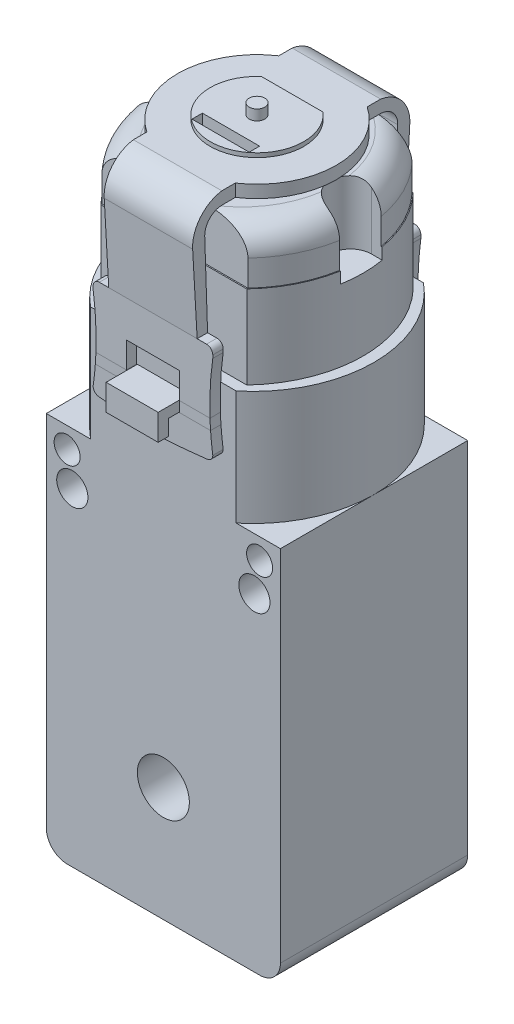
SolidWorks part; units mm, degrees
ref_plane "Alzado" through (0, 0, 0) normal (0, 0, 1) x (1, 0, 0)
ref_plane "Planta" through (0, 0, 0) normal (0, 1, 0) x (1, 0, 0)
ref_plane "Vista lateral" through (0, 0, 0) normal (1, 0, 0) x (0, 0, -1)
sketch "Croquis1" plane through (0, 0, 0) normal (0, 0, 1) x (1, 0, 0)
  line L0 (0, 17.25) -> (0, -19.25)
  line L1 (-11.25, 17.25) -> (11.25, 17.25)
  line L2 (11.25, 17.25) -> (11.25, -17.25)
  line L3 (9.25, -19.25) -> (-9.25, -19.25)
  line L4 (-11.25, 17.25) -> (-11.25, -17.25)
  arc A0 (11.25, -17.25) -> (9.25, -19.25) centre (9.25, -17.25) cw
  circle A1 centre (9.25, 15.25) radius 1.25
  circle A2 centre (8.75, 12.25) radius 1.5
  arc A3 (-11.25, -17.25) -> (-9.25, -19.25) centre (-9.25, -17.25) ccw
  circle A4 centre (-8.75, 12.25) radius 1.5
  circle A5 centre (-9.25, 15.25) radius 1.25
  point P9 (11.25, -19.25)
  dimension "D3" = 2
  dimension "D4" = 2.5
  dimension "D5" = 3
  dimension "D1" = 11.25
  dimension "D2" = 36.5
  dimension "D6" = 2
  dimension "D7" = 2.5
  dimension "D8" = 2
  dimension "D9" = 5
extrude "Saliente-Extruir1" add sketch "Croquis1" along normal blind 9 and the other way blind 9 contours L4 A3 L3 L0 L1 A4 A5 | A0 L2 L1 L0 L3 A2 A1 region at (5.5136, -1.3976, 0) region at (-5.5136, -1.3976, 0)
sketch "Croquis2" plane through (0, 17.25, 0) normal (0, 1, 0) x (1, 0, 0)
  line L0 (0, 9) -> (0, 0) construction
  line L1 (-11.25, 9) -> (11.25, 9) construction
  line L2 (-7, 9) -> (7, 9)
  line L3 (0, 0) -> (7, 0) construction
  line L4 (-7, -9) -> (7, -9)
  arc A0 (7, 9) -> (7, -9) centre (-0.4044, 0) cw
  arc A1 (-7, 9) -> (-7, -9) centre (0.4044, 0) ccw
  point P11 (0, -9)
  dimension "D1" = 7
extrude "Saliente-Extruir2" add sketch "Croquis2" along normal blind 11
sketch "Croquis3" plane through (0, 0, 0) normal (0, 0, 1) x (1, 0, 0)
  line L0 (0, -19.25) -> (0, -24.25) construction
  line L1 (9.25, -19.25) -> (-9.25, -19.25) construction
  line L2 (-2.5, -19.25) -> (2.5, -19.25)
  line L3 (2.5, -19.25) -> (2.5, -24.25)
  line L4 (2.5, -24.25) -> (-2.5, -24.25)
  line L5 (-2.5, -19.25) -> (-2.5, -24.25)
  circle A0 centre (0, -21.75) radius 1.25
  dimension "D3" = 2.5
  dimension "D1" = 2.5
  dimension "D2" = 5
extrude "Saliente-Extruir3" add sketch "Croquis3" along normal blind 1.5 and the other way blind 1.5
fillet "Redondeo1" radius 0.3 2 edges at (-2.5, -19.25, 0) (2.5, -19.25, 0)
sketch "Croquis4" plane through (0, 0, 0) normal (0, 0, 1) x (1, 0, 0)
  line L0 (9.25, -19.25) -> (-9.25, -19.25) construction
  line L1 (-3.337, -10.75) -> (3.722, -10.75) construction
  line L3 (0, 0) -> (0, -9.56) construction
  line L4 (-3.337, -5.75) -> (4.3804, -5.75) construction
  line L5 (11.25, 17.25) -> (7, 17.25) construction
  circle A0 centre (0, -8.25) radius 2.5
  dimension "D1" = 5
  dimension "D2" = 23
  dimension "D3" = 8.5
extrude "Cortar-Extruir1" cut sketch "Croquis4" against normal blind 10 and the other way blind 10
sketch "Croquis5" plane through (0, 0, -9) normal (0, 0, -1) x (-1, 0, 0)
  line L0 (0, 0) -> (0, 13.3907) construction
  line L1 (11.25, 17.25) -> (11.25, -17.25) construction
  line L2 (11.25, 17.25) -> (7, 17.25) construction
  line L3 (-9.25, -19.25) -> (9.25, -19.25) construction
  circle A0 centre (9.75, -2.25) radius 0.75
  circle A1 centre (9.25, -17.25) radius 1
  circle A3 centre (-9.25, -17.25) radius 1
  circle A4 centre (-9.75, -2.25) radius 0.75
  dimension "D1" = 1.5
  dimension "D4" = 2
  dimension "D2" = 1.5
  dimension "D3" = 19.5
  dimension "D5" = 2
  dimension "D6" = 2
extrude "Cortar-Extruir2" cut sketch "Croquis5" against normal blind 1.5
sketch "Croquis6" plane through (0, 0, -9) normal (0, 0, -1) x (-1, 0, 0)
  line L0 (0, 0) -> (0, 13.134) construction
  line L1 (-2.8, -19.25) -> (2.8, -19.25) construction
  circle A0 centre (0, 2.75) radius 2
  dimension "D1" = 4
  dimension "D2" = 22
extrude "Saliente-Extruir4" add sketch "Croquis6" along normal blind 2
sketch "Croquis7" plane through (0, 0, -9) normal (0, 0, -1) x (-1, 0, 0)
  line L2 (-3.0823, -11.75) -> (2.3777, -11.75) construction
  line L3 (-9.25, -19.25) -> (9.25, -19.25) construction
  circle A0 centre (0, -8.25) radius 3.5
  circle A1 centre (0, -8.25) radius 2.5
  dimension "D2" = 7.5
extrude "Saliente-Extruir5" add sketch "Croquis7" along normal blind 0.2
sketch "Croquis8" plane through (0, 28.25, 0) normal (0, 1, 0) x (1, 0, 0)
  line L0 (-7.0162, -8) -> (7.0162, -8)
  line L1 (-7, -9) -> (7, -9) construction
  line L2 (0, 0) -> (4.714, 0) construction
  line L3 (0, 0) -> (0, 4.6921) construction
  line L4 (-7.0162, 8) -> (7.0162, 8)
  line L5 (7.0162, 9) -> (7.0162, 6.4394) construction
  line L6 (7, 9) -> (11.25, 9) construction
  arc A0 (7.0162, 8) -> (7.0162, -8) centre (-1.4527, 0) cw
  arc A3 (-7.0162, 8) -> (-7.0162, -8) centre (1.4527, 0) ccw
  point P4 (0, -8)
  dimension "D3" = 11.65
  dimension "D1" = 1
extrude "Cortar-Extruir5" cut sketch "Croquis8" against normal blind 10
sketch "Croquis9" plane through (0, 0, 0) normal (0, 0, 1) x (1, 0, 0)
  line L0 (0, 28.25) -> (0, 16.5993) construction
  line L1 (-7, 28.25) -> (7, 28.25) construction
  line L2 (-2.9593, 24.7222) -> (3.0407, 24.7222)
  line L3 (3.0407, 24.7222) -> (3.0407, 21.7222)
  line L4 (3.0407, 21.7222) -> (-2.9593, 21.7222)
  line L5 (-2.9593, 21.7222) -> (-2.9593, 24.7222)
  dimension "D1" = 6
  dimension "D2" = 3
extrude "Cortar-Extruir6" cut sketch "Croquis9" against normal blind 10 and the other way blind 10
sketch "Croquis11" plane through (0, 0, 0) normal (1, 0, 0) x (0, 0, -1)
  line L0 (-9, 24.7222) -> (-11, 24.7222)
  line L1 (-11, 24.7222) -> (-11, 23.2222)
  line L2 (-11, 23.2222) -> (-12, 23.2222)
  line L3 (-12, 23.2222) -> (-12, 25.7222)
  line L4 (-12, 25.7222) -> (-9, 25.7222)
  line L5 (-9, 28.25) -> (-9, 17.25) construction
  line L6 (-9, 25.7222) -> (-9, 24.7222)
  dimension "D1" = 2
  dimension "D2" = 1.5
  dimension "D3" = 1
  dimension "D4" = 2.5
extrude "Saliente-Extruir6" add sketch "Croquis11" along normal blind 2.5 and the other way blind 2.5
mirror "Simetría1" about plane through (0, 0, 0) normal (0, 0, 1) of "Saliente-Extruir6"
sketch "Croquis12" plane through (0, 18.25, 0) normal (0, 1, 0) x (1, 0, 0)
  line L0 (-7.0162, 8) -> (7.0162, 8)
  line L1 (7.0162, -8) -> (-7.0162, -8)
  arc A0 (-7.0162, 8) -> (-7.0162, -8) centre (1.4527, 0) ccw
  arc A1 (7.0162, 8) -> (7.0162, -8) centre (-1.4527, 0) cw
extrude "Saliente-Extruir7" add sketch "Croquis12" along normal blind 18 separate body
sketch "Croquis13" plane through (0, 36.25, 0) normal (0, 1, 0) x (1, 0, 0)
  line L0 (-7.0162, 7.8859) -> (7.0162, 7.8859)
  line L1 (0, 0) -> (4.4298, 0) construction
  line L2 (-7.0162, -7.8859) -> (7.0162, -7.8859)
  line L3 (0, 0) -> (0, 5.9901) construction
  line L4 (-7.0162, 8) -> (-7.0162, 7.2605) construction
  line L5 (7.0162, 8) -> (7.0162, 7.0975) construction
  arc A0 (7.0162, 7.8859) -> (7.0162, -7.8859) centre (-1.4696, 0) cw
  arc A1 (-7.0162, 7.8859) -> (-7.0162, -7.8859) centre (1.4696, 0) ccw
extrude "Saliente-Extruir8" add sketch "Croquis13" along normal blind 5
fillet "Redondeo2" radius 2.5 2 edges at (-10.1147, 41.25, 0) (10.1147, 41.25, 0)
sketch "Croquis14" plane through (0, 41.25, 0) normal (0, 1, 0) x (1, 0, 0)
  line L0 (-2.964, 3.3859) -> (2.964, 3.3859)
  line L1 (3.0401, 7.8859) -> (-3.0401, 7.8859) construction
  line L2 (0, 0) -> (0, 6.8306) construction
  line L3 (0, 0) -> (0, -5.8728) construction
  line L4 (-2.75, -2.4984) -> (2.75, -2.4984)
  line L5 (2.75, -2.4984) -> (2.75, -3.4984)
  line L6 (-2.75, -2.4984) -> (-2.75, -3.4984)
  line L7 (-2.75, -3.4984) -> (2.75, -3.4984)
  arc A0 (-2.964, 3.3859) -> (2.964, 3.3859) centre (0, 0) ccw
  point P12 (0, -2.4984)
  dimension "D1" = 9
  dimension "D2" = 4.5
  dimension "D3" = 5.5
  dimension "D4" = 1
extrude "Saliente-Extruir9" add sketch "Croquis14" along normal blind 2 separate body contours L0 A0 L7 L6 L4 L5 region at (0, 41.25, 0.0162)
sketch "Croquis15" plane through (0, 43.25, 0) normal (0, 1, 0) x (1, 0, 0)
  circle A0 centre (0, 0) radius 0.75
  dimension "D1" = 1.5
extrude "Saliente-Extruir10" add sketch "Croquis15" along normal blind 1 separate body
sketch "Croquis16" plane through (0, 0, -9) normal (0, 0, -1) x (-1, 0, 0)
  line L0 (0, 0) -> (0, 20.8797) construction
  line L1 (2.349, 16.9) -> (8.25, 16.9) construction
  line L2 (11.25, 17.25) -> (7, 17.25) construction
  line L3 (11.25, 17.25) -> (11.25, -17.25) construction
  circle A0 centre (5.9941, 14.65) radius 2.25
  circle A1 centre (-5.9941, 14.65) radius 2.25
  dimension "D1" = 4.5
  dimension "D2" = 0.35
  dimension "D3" = 3
extrude "Cortar-Extruir7" cut sketch "Croquis16" against normal blind 2
sketch "Croquis17" plane through (0, 0, -7) normal (0, 0, -1) x (-1, 0, 0)
  line L0 (6.2973, 16.3735) -> (6.2973, 14.95)
  line L1 (6.2973, 14.95) -> (7.7182, 14.95)
  line L2 (5.9941, 14.65) -> (5.9941, 16.7103) construction
  line L3 (5.9941, 14.65) -> (8.0852, 14.65) construction
  line L4 (5.6908, 14.95) -> (4.27, 14.95)
  line L5 (5.6908, 16.3735) -> (5.6908, 14.95)
  line L6 (5.6908, 14.35) -> (4.27, 14.35)
  line L7 (5.6908, 12.9265) -> (5.6908, 14.35)
  line L8 (6.2973, 14.35) -> (7.7182, 14.35)
  line L9 (6.2973, 12.9265) -> (6.2973, 14.35)
  circle A0 centre (5.9941, 14.65) radius 1.75
  dimension "D1" = 3.5
  dimension "D2" = 0.3032
  dimension "D3" = 0.3
extrude "Saliente-Extruir11" add sketch "Croquis17" along normal blind 1.8 contours L5 A0 L4 | L1 A0 L0 | L9 A0 L8 | L0 A0 L5 L4 L6 L7 L9 L8 L1 | L6 A0 L7 region at (-6.8694, 15.523, -7) region at (-5.9941, 14.65, -7) region at (-5.1188, 15.523, -7) region at (-6.8694, 13.777, -7) region at (-5.1188, 13.777, -7)
sketch "Croquis18" plane through (0, 0, -8.8) normal (0, 0, -1) x (-1, 0, 0)
  line L0 (5.9941, 16.4) -> (5.9941, 14.65) construction
  line L1 (5.9941, 14.65) -> (7.7441, 14.65) construction
  line L2 (6.2941, 16.1877) -> (6.2941, 14.95)
  line L3 (6.2941, 14.95) -> (7.5318, 14.95)
  line L4 (5.6941, 14.95) -> (4.4563, 14.95)
  line L5 (5.6941, 16.1877) -> (5.6941, 14.95)
  line L6 (5.6941, 14.35) -> (4.4563, 14.35)
  line L7 (5.6941, 13.1123) -> (5.6941, 14.35)
  line L8 (6.2941, 13.1123) -> (6.2941, 14.35)
  line L9 (6.2941, 14.35) -> (7.5318, 14.35)
  circle A0 centre (5.9941, 14.65) radius 1.75 construction
  circle A1 centre (5.9941, 14.65) radius 1.75 construction
  arc A6 (4.4563, 14.95) -> (4.4563, 14.35) centre (5.9941, 14.65) ccw
  arc A7 (6.2941, 16.1877) -> (5.6941, 16.1877) centre (5.9941, 14.65) ccw
  arc A8 (7.5318, 14.35) -> (7.5318, 14.95) centre (5.9941, 14.65) ccw
  arc A9 (5.6941, 13.1123) -> (6.2941, 13.1123) centre (5.9941, 14.65) ccw
  dimension "D1" = 0.3
  dimension "D2" = 0.3
extrude "Cortar-Extruir8" cut sketch "Croquis18" against normal blind 0.5 contours L4 A6 L6 L7 A9 L8 L9 A8 L3 L2 A7 L5
mirror "Simetría4" about plane through (0, 0, 0) normal (1, 0, 0) of "Saliente-Extruir11"
mirror "Simetría5" about plane through (0, 0, 0) normal (1, 0, 0) of "Cortar-Extruir8"
ref_plane "Plano1" through (0, 41.65, 0) normal (0, 1, 0) x (1, 0, 0)
sketch "Croquis20" plane through (0, 41.65, 0) normal (0, 1, 0) x (1, 0, 0)
  line L0 (-2.964, 3.3859) -> (2.964, 3.3859)
  line L1 (-2.75, -3.4984) -> (-2.75, -2.4984)
  line L2 (-2.75, -2.4984) -> (2.75, -2.4984)
  line L3 (2.75, -2.4984) -> (2.75, -3.4984)
  line L4 (2.75, -3.4984) -> (-2.75, -3.4984)
  circle A0 centre (0, 0) radius 7.6307
  circle A1 centre (0, 0) radius 4.5
extrude "Saliente-Extruir13" add sketch "Croquis20" along normal blind 1.2 separate body contours A0 A1 | L0 A1 region at (0, 41.65, -3.8366) region at (-7.4148, 41.65, 0)
sketch "Croquis19" plane through (0, 0, 0) normal (1, 0, 0) x (0, 0, -1)
  line L0 (0, 0) -> (0, 53.3017) construction
  line L1 (9, 21.7222) -> (9, 24.7222)
  line L2 (9, 28.25) -> (9, 17.25) construction
  line L3 (12, 23.2222) -> (11, 23.2222) construction
  line L4 (9, 21.7222) -> (10, 21.7222)
  line L5 (10, 31.7222) -> (10, 25.8545)
  line L6 (9, 31.7222) -> (9.2741, 39.8972)
  line L7 (10, 21.7222) -> (10, 24.7222)
  line L9 (10, 21.7222) -> (10, 31.7222)
  line L10 (10, 31.7222) -> (10.4333, 39.3872)
  line L17 (9, 24.7222) -> (10, 24.7222)
  line L20 (9, 25.7222) -> (10, 25.7222)
  line L21 (10, 25.7222) -> (10, 25.8545)
  line L22 (9, 25.7222) -> (9, 31.7222)
  line L25 (-4.5012, 42.8648) -> (-4.5012, 41.7894)
  line L26 (8.3762, 41.65) -> (-8.3762, 41.65) construction
  line L29 (7.6307, 41.65) -> (7.6307, 42.85) construction
  line L30 (7.6307, 42.85) -> (7.6307, 41.65)
  line L31 (-10, 21.7222) -> (-10, 24.7222)
  line L32 (-9, 24.7222) -> (-10, 24.7222)
  line L33 (-9, 21.7222) -> (-9, 24.7222)
  line L34 (-9, 21.7222) -> (-10, 21.7222)
  line L35 (-10, 31.7222) -> (-10.4333, 39.3872)
  line L36 (-7.6307, 42.85) -> (-7.6307, 41.65)
  line L37 (-9, 31.7222) -> (-9.2741, 39.8972)
  line L38 (-9, 25.7222) -> (-9, 31.7222)
  line L39 (-9, 25.7222) -> (-10, 25.7222)
  line L40 (-10, 25.7222) -> (-10, 25.8545)
  line L41 (-10, 31.7222) -> (-10, 25.8545)
  arc A0 (9.2741, 39.8972) -> (7.6307, 41.65) centre (7.5783, 39.9541) ccw
  arc A1 (7.6307, 42.85) -> (10.4333, 39.3872) centre (7.1238, 39.5743) cw
  arc A2 (-7.6307, 42.85) -> (-10.4333, 39.3872) centre (-7.1238, 39.5743) ccw
  arc A3 (-9.2741, 39.8972) -> (-7.6307, 41.65) centre (-7.5783, 39.9541) cw
  dimension "D1" = 10
  dimension "D2" = 1.5
  dimension "D3" = 1
  dimension "D4" = 8.175
extrude "Saliente-Extruir12" add sketch "Croquis19" along normal blind 5.75 and the other way blind 5.75 separate body contours L6 L22 L20 L9 L5 L10 | L17 L1 L4 L7 | L25 L35 | L32 | L31 L32 L33 L34 region at (0, 34.7182, -9.4971) region at (0, 23.2222, -9.5) region at (0, 34.7182, 9.4971)
ref_plane "Plano2" through (0, 0, 10) normal (0, 0, 1) x (1, 0, 0)
sketch "Croquis23" plane through (0, 0, 10) normal (0, 0, 1) x (1, 0, 0)
  line L0 (0, 31.7222) -> (4.25, 31.7222)
  line L1 (-5.75, 31.7222) -> (5.75, 31.7222) construction
  line L2 (4.25, 31.7222) -> (4.25, 42.85)
  line L3 (-5.75, 42.85) -> (5.75, 42.85) construction
  line L4 (4.25, 42.85) -> (5.75, 42.85)
  line L5 (5.75, 42.85) -> (5.75, 31.7222)
  line L6 (5.75, 31.7222) -> (4.25, 31.7222)
  line L7 (0, 31.7222) -> (0, 41.8289) construction
  line L9 (-5.75, 31.7222) -> (-4.25, 31.7222)
  line L10 (-5.75, 42.85) -> (-5.75, 31.7222)
  line L11 (-4.25, 42.85) -> (-5.75, 42.85)
  line L12 (-4.25, 31.7222) -> (-4.25, 42.85)
  dimension "D1" = 4.25
extrude "Cortar-Extruir9" cut sketch "Croquis23" against normal blind 1.8 and the other way blind 1 contours L9 L12 L11 L10 | L6 L5 L4 L2 region at (5, 37.2861, 10) region at (-5, 37.2861, 10)
ref_plane "Plano3" through (0, 0, -10) normal (0, 0, 1) x (1, 0, 0)
sketch "Croquis24" plane through (0, 0, -10) normal (0, 0, 1) x (1, 0, 0)
  line L0 (0, 39.3872) -> (0, 31.7222) construction
  line L1 (-5.75, 39.3872) -> (5.75, 39.3872) construction
  line L2 (-5.75, 31.7222) -> (5.75, 31.7222) construction
  line L3 (0, 31.7222) -> (-4.25, 31.7222)
  line L4 (-4.25, 31.7222) -> (-4.25, 42.85)
  line L5 (-5.75, 42.85) -> (5.75, 42.85) construction
  line L6 (-4.25, 42.85) -> (-5.75, 42.85)
  line L7 (-5.75, 42.85) -> (-5.75, 31.7222)
  line L8 (-5.75, 31.7222) -> (-4.25, 31.7222)
  line L9 (4.25, 42.85) -> (5.75, 42.85)
  line L10 (5.75, 31.7222) -> (4.25, 31.7222)
  line L11 (5.75, 42.85) -> (5.75, 31.7222)
  line L12 (4.25, 31.7222) -> (4.25, 42.85)
  dimension "D1" = 4.25
extrude "Cortar-Extruir10" cut sketch "Croquis24" along normal blind 1.8 and the other way blind 1.8 contours L7 L8 L4 L6 | L12 L10 L11 L9 region at (-5, 37.2861, -10) region at (5, 37.2861, -10)
sketch "Croquis21" plane through (0, 0, 10) normal (0, 0, 1) x (1, 0, 0)
  line L0 (0, 31.7222) -> (0, 21.7222) construction
  line L2 (-4.25, 31.7222) -> (4.25, 31.7222) construction
  line L3 (-5.75, 21.7222) -> (5.75, 21.7222) construction
  line L4 (-5.75, 25.7222) -> (-2.558, 25.7222)
  line L6 (-2.558, 24.7222) -> (-5.75, 24.7222)
  line L7 (-5.75, 24.7222) -> (-5.75, 25.7222)
  line L8 (2.558, 24.7222) -> (5.75, 24.7222)
  line L10 (5.75, 25.7222) -> (2.558, 25.7222)
  line L11 (5.75, 24.7222) -> (5.75, 25.7222)
  line L12 (2.558, 25.7222) -> (2.558, 24.7222)
  line L14 (-2.558, 25.7222) -> (-2.558, 24.7222)
extrude "Saliente-Extruir17" add sketch "Croquis21" against normal blind 1 separate body
sketch "Croquis26" plane through (0, 0, -10) normal (0, 0, -1) x (-1, 0, 0)
  line L0 (-5.75, 25.7222) -> (-5.75, 24.7222)
  line L1 (-5.75, 24.7222) -> (-2.56, 24.7222)
  line L3 (-2.56, 25.7222) -> (-5.75, 25.7222)
  line L4 (2.56, 25.7222) -> (5.75, 25.7222)
  line L5 (5.75, 25.7222) -> (5.75, 24.7222)
  line L6 (5.75, 24.7222) -> (2.56, 24.7222)
  line L10 (2.56, 25.7222) -> (2.56, 24.7222)
  line L11 (2.5, 25.7222) -> (2.5, 23.2222) construction
  line L12 (-2.56, 25.7222) -> (-2.56, 24.7222)
  line L13 (-2.5, 24.7222) -> (-2.5, 25.7222) construction
  dimension "D1" = 0.06
  dimension "D2" = 0.06
extrude "Saliente-Extruir18" add sketch "Croquis26" against normal blind 1 separate body
sketch "Croquis27" plane through (0, 0, 10) normal (0, 0, 1) x (1, 0, 0)
  line L0 (0, 31.7222) -> (0, 21.7222) construction
  line L5 (-4.25, 31.7222) -> (4.25, 31.7222) construction
  line L6 (5.75, 31.7222) -> (5.75, 25.7222) construction
  line L7 (5.75, 21.7222) -> (5.75, 24.7222) construction
  line L8 (5.75, 30.8317) -> (5.75, 22.7628)
  line L9 (-5.75, 30.8317) -> (-5.75, 22.7628)
  line L16 (5.75, 22.242) -> (5.75, 21.7222)
  line L19 (0, 21.7222) -> (5.75, 21.7222)
  arc A0 (5.75, 30.8317) -> (5.75, 22.7628) centre (33.9574, 26.7973) ccw
  arc A1 (-5.75, 30.8317) -> (-5.75, 22.7628) centre (-33.9574, 26.7973) cw
  arc A3 (5.75, 22.242) -> (0, 21.7222) centre (-4.9159, 108.1594) cw
extrude "Cortar-Extruir13" cut sketch "Croquis27" against normal blind 1
sketch "Croquis28" plane through (0, 0, 10) normal (0, 0, 1) x (1, 0, 0)
  line L0 (0, 21.7222) -> (-5.75, 21.7222)
  line L1 (-5.75, 21.7222) -> (-5.75, 22.242)
  line L2 (-5.75, 21.7222) -> (-5.75, 22.7628) construction
  line L3 (0, 21.7222) -> (0, 26.4064) construction
  arc A1 (0, 21.7222) -> (-5.75, 22.242) centre (4.9159, 108.1594) cw
extrude "Cortar-Extruir14" cut sketch "Croquis28" against normal blind 1
sketch "Croquis29" plane through (0, 0, 10) normal (0, 0, 1) x (1, 0, 0)
  line L0 (-2.558, 25.7222) -> (-2.558, 28.2222)
  line L1 (-2.558, 28.2222) -> (2.558, 28.2222)
  line L2 (2.558, 28.2222) -> (2.558, 25.7222)
  line L3 (-5.4832, 25.7222) -> (5.4832, 25.7222) construction
  line L4 (-2.558, 25.7222) -> (2.558, 25.7222)
  dimension "D1" = 2.5
extrude "Cortar-Extruir15" cut sketch "Croquis29" against normal blind 1
sketch "Croquis30" plane through (0, 0, -10) normal (0, 0, -1) x (-1, 0, 0)
  line L0 (2.56, 25.7222) -> (2.56, 28.2222)
  line L1 (2.56, 28.2222) -> (-2.56, 28.2222)
  line L2 (-2.56, 28.2222) -> (-2.56, 25.7222)
  line L3 (-2.56, 25.7222) -> (2.56, 25.7222)
  dimension "D1" = 2.5
extrude "Cortar-Extruir16" cut sketch "Croquis30" against normal blind 1
sketch "Croquis31" plane through (0, 0, -10) normal (0, 0, -1) x (-1, 0, 0)
  line L0 (-5.75, 30.8317) -> (-5.75, 22.7628)
  line L1 (0, 28.2222) -> (0, 24.0678) construction
  line L2 (-2.558, 28.2222) -> (2.558, 28.2222) construction
  line L3 (-3.0407, 21.7222) -> (2.9593, 21.7222) construction
  line L4 (-5.75, 22.242) -> (-5.75, 21.7222)
  line L5 (-5.75, 21.7222) -> (-0.0407, 21.7222)
  line L6 (5.75, 30.8317) -> (5.75, 22.7628)
  arc A1 (-5.75, 30.8317) -> (-5.4832, 25.7222) centre (-36.3108, 26.6744) cw
  arc A2 (-5.4832, 25.7222) -> (-5.5386, 24.7222) centre (-25.9693, 26.355) cw
  arc A3 (-5.5386, 24.7222) -> (-5.75, 22.7628) centre (-40.9674, 27.5536) cw
  arc A4 (-5.75, 22.242) -> (-0.0407, 21.7222) centre (5.0478, 109.2223) ccw
  arc A5 (5.5386, 24.7222) -> (5.75, 22.7628) centre (40.9674, 27.5536) ccw
  arc A6 (5.4832, 25.7222) -> (5.5386, 24.7222) centre (25.9693, 26.355) ccw
  arc A7 (5.75, 30.8317) -> (5.4832, 25.7222) centre (36.3108, 26.6744) ccw
extrude "Cortar-Extruir17" cut sketch "Croquis31" against normal blind 1
sketch "Croquis32" plane through (0, 0, -10) normal (0, 0, -1) x (-1, 0, 0)
  line L0 (0, 31.7222) -> (0, 24.5256) construction
  line L1 (4.25, 31.7222) -> (-4.25, 31.7222) construction
  line L2 (0, 21.7222) -> (5.75, 21.7222)
  line L3 (5.75, 21.7222) -> (5.75, 22.242)
  arc A0 (5.75, 22.242) -> (0, 21.7222) centre (-4.9159, 108.1594) cw
extrude "Cortar-Extruir18" cut sketch "Croquis32" against normal blind 1
sketch "Croquis33" plane through (0, 41.65, 0) normal (0, 1, 0) x (1, 0, 0)
  line L0 (-4.25, 8.2) -> (-4.25, 7.6307)
  line L1 (-5.75, 7.6307) -> (5.75, 7.6307) construction
  line L2 (-4.25, 7.6307) -> (-5.75, 7.6307)
  line L3 (-5.75, 7.6307) -> (-5.75, 8.2)
  line L4 (-5.75, 8.2) -> (-4.25, 8.2)
  line L5 (0, 0) -> (0, 9.2428) construction
  line L6 (5.75, 7.6307) -> (5.75, 8.2)
  line L7 (4.25, 8.2) -> (4.25, 7.6307)
  line L8 (5.75, 8.2) -> (4.25, 8.2)
  line L9 (4.25, 7.6307) -> (5.75, 7.6307)
  line L10 (0, 0) -> (6.7492, 0) construction
  line L11 (-5.75, -7.6307) -> (-5.75, -8.2)
  line L12 (-5.75, -8.2) -> (-4.25, -8.2)
  line L13 (-4.25, -8.2) -> (-4.25, -7.6307)
  line L14 (-4.25, -7.6307) -> (-5.75, -7.6307)
  line L15 (4.25, -8.2) -> (4.25, -7.6307)
  line L16 (5.75, -7.6307) -> (5.75, -8.2)
  line L17 (5.75, -8.2) -> (4.25, -8.2)
  line L18 (4.25, -7.6307) -> (5.75, -7.6307)
extrude "Cortar-Extruir19" cut sketch "Croquis33" along normal blind 1.5 and the other way blind 0.3
sketch "Croquis34" plane through (0, 41.65, 0) normal (0, 1, 0) x (1, 0, 0)
  line L0 (-4.25, 7.6307) -> (-4.25, 6.3376)
  line L1 (4.25, 7.6307) -> (4.25, 6.3376)
  line L2 (-4.25, 7.6307) -> (4.25, 7.6307)
  line L3 (0, 0) -> (4.9503, 0) construction
  line L4 (-4.25, -7.6307) -> (-4.25, -6.3376)
  line L5 (-4.25, -7.6307) -> (4.25, -7.6307)
  line L6 (4.25, -7.6307) -> (4.25, -6.3376)
  arc A0 (-4.25, -6.3376) -> (4.25, -6.3376) centre (0, 0) ccw
  arc A1 (4.25, 6.3376) -> (-4.25, 6.3376) centre (0, 0) ccw
extrude "Saliente-Extruir19" add sketch "Croquis34" along normal blind 1.2 contours A1 L2 L0 | A1 L1 L2 | A0 L4 L5 | A0 L5 L6 region at (-3.2063, 41.65, -7.2491) region at (3.2063, 41.65, -7.2491) region at (3.2063, 41.65, 7.2491) region at (-3.2063, 41.65, 7.2491)
fillet "Redondeo3" radius 0.6 2 edges at (-5.75, 31.7222, 9.5) (5.75, 31.7222, 9.5)
fillet "Redondeo4" radius 0.6 2 edges at (-5.75, 22.242, 9.5) (5.75, 22.242, 9.5)
fillet "Redondeo5" radius 0.6 2 edges at (5.75, 31.7222, -9.5) (-5.75, 31.7222, -9.5)
fillet "Redondeo6" radius 0.6 2 edges at (-5.75, 22.242, -9.5) (5.75, 22.242, -9.5)
sketch "Croquis35" plane through (0, 41.65, 0) normal (0, 1, 0) x (1, 0, 0)
  line L0 (0, 0) -> (0, 5.9489) construction
  line L1 (0, 0) -> (14.0423, 0) construction
  line L3 (9.9408, 2) -> (9.0008, 2)
  line L4 (9.9408, -2) -> (9.0008, -2)
  line L5 (9.9408, 2) -> (10.0244, 2)
  line L6 (9.9408, -2) -> (10.0244, -2)
  line L7 (-9.9408, 2) -> (-10.0244, 2)
  line L8 (-9.9408, -2) -> (-10.0244, -2)
  line L9 (-9.9408, -2) -> (-9.0008, -2)
  line L10 (-9.9408, 2) -> (-9.0008, 2)
  arc A0 (7.0162, -7.8859) -> (7.0162, 7.8859) centre (-1.4696, 0) ccw construction
  arc A1 (9.0008, 2) -> (9.0008, -2) centre (9.0008, 0) ccw
  arc A3 (7.0162, -8) -> (7.0162, 8) centre (-1.4527, 0) ccw construction
  arc A4 (10.0244, 2) -> (10.0244, -2) centre (-1.4527, 0) cw
  arc A5 (-10.0244, 2) -> (-10.0244, -2) centre (1.4527, 0) ccw
  arc A6 (-9.0008, 2) -> (-9.0008, -2) centre (-9.0008, 0) cw
  point P11 (9.9408, 0)
  dimension "D1" = 2
  dimension "D2" = 0.94
extrude "Cortar-Extruir20" cut sketch "Croquis35" against normal blind 6.5
